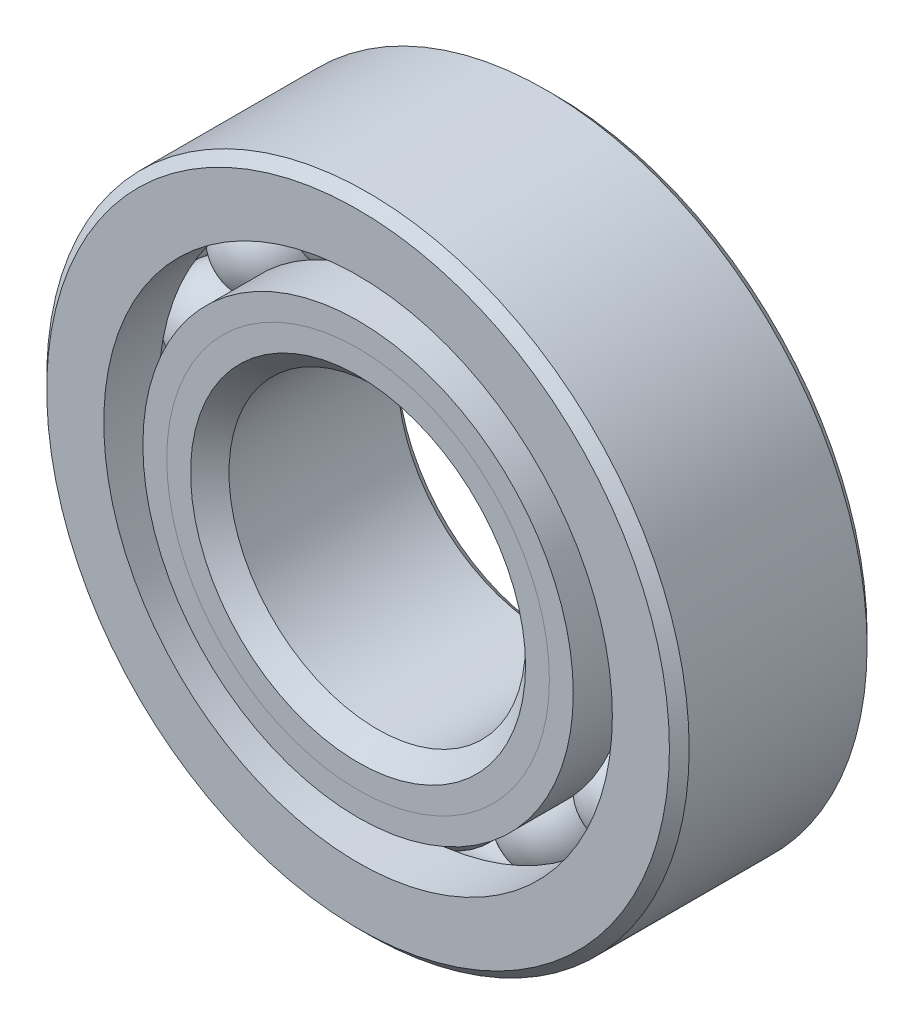
SolidWorks part; units mm, degrees
ref_plane "Front Plane" through (0, 0, 0) normal (0, 0, 1) x (1, 0, 0)
ref_plane "Top Plane" through (0, 0, 0) normal (0, 1, 0) x (1, 0, 0)
ref_plane "Right Plane" through (0, 0, 0) normal (1, 0, 0) x (0, 0, -1)
sketch "Sketch1" plane through (0, 0, 0) normal (1, 0, 0) x (0, 0, -1)
  line L0 (-6.35, 0) -> (6.35, 0) construction
  line L1 (0, 20.6375) -> (0, -20.6375) construction
  line L2 (5.715, 20.6375) -> (-5.715, 20.6375)
  line L3 (-5.715, 20.6375) -> (-6.35, 20.0025)
  line L4 (-6.35, 20.0025) -> (-6.35, 16.3373)
  line L5 (-6.35, 16.3373) -> (-2.8222, 16.3373)
  line L6 (6.35, 16.3373) -> (2.8222, 16.3373)
  line L7 (6.35, 20.0025) -> (6.35, 16.3373)
  line L8 (5.715, 20.6375) -> (6.35, 20.0025)
  line L9 (0, 20.6375) -> (0, 15.0813) construction
  line L10 (0, 15.0813) -> (0, 9.525) construction
  arc A0 (-2.8222, 16.3373) -> (2.8222, 16.3373) centre (0, 15.0813) cw
  point P14 (0, 9.525)
  dimension "D3" = 5.6444
  dimension "D1" = 45
  dimension "Width" = 12.7
  dimension "OD" = 41.275
  dimension "D2" = 0.635
  dimension "Shaft Dia" = 19.05
  dimension "D4" = 1.256
revolve "Revolve1" add sketch "Sketch1" angle 360 about L0
sketch "Sketch2" plane through (0, 0, 0) normal (1, 0, 0) x (0, 0, -1)
  line L0 (-6.35, 13.8252) -> (-2.8222, 13.8252)
  line L1 (-6.35, 20.0025) -> (-6.35, -20.0025) construction
  line L2 (-6.35, 13.8252) -> (-6.35, 12.2919)
  line L3 (-6.35, 12.2919) -> (-4.8167, 10.7586)
  line L4 (-4.8167, 10.7586) -> (0, 10.7586)
  line L5 (0, 20.6375) -> (0, -20.6375) construction
  line L6 (0, 10.7586) -> (0, 11.9921)
  line L7 (0, 11.9921) -> (0, 9.525) construction
  line L8 (-6.35, 13.8252) -> (-6.35, 10.7586) construction
  line L9 (-6.35, 10.7586) -> (-4.8167, 10.7586) construction
  arc A0 (-2.8222, 13.8252) -> (0, 11.9921) centre (0, 15.0813) ccw
  arc A1 (2.8222, 16.3373) -> (-2.8222, 16.3373) centre (0, 15.0813) ccw construction
  circle A2 centre (0, 15.0813) radius 3.0891 construction
  dimension "D1" = 45
revolve "Revolve2" add sketch "Sketch2" angle 360 about L0
sketch "Sketch3" plane through (0, 0, 0) normal (1, 0, 0) x (0, 0, -1)
  line L0 (-6.35, 12.2919) -> (-4.8167, 10.7586)
  line L1 (-4.8167, 10.7586) -> (0, 10.7586)
  line L2 (0, 10.7586) -> (0, 11.9921)
  line L3 (-6.35, 12.2919) -> (-6.35, 10.7586)
  line L4 (-6.35, 13.8252) -> (-6.35, 10.7586) construction
  line L5 (-6.35, 10.7586) -> (-5.1164, 9.525)
  line L6 (-5.1164, 9.525) -> (5.715, 9.525)
  line L7 (5.715, 20.6375) -> (5.715, -20.6375) construction
  line L8 (5.715, 9.525) -> (6.35, 10.16)
  line L9 (6.35, -20.0025) -> (6.35, 20.0025) construction
  line L10 (6.35, 10.16) -> (6.35, 13.8252)
  line L11 (6.35, 13.8252) -> (2.8222, 13.8252)
  line L13 (5.715, 20.6375) -> (6.35, 20.0025) construction
  circle A0 centre (0, 15.0813) radius 3.0891 construction
  arc A1 (2.8222, 13.8252) -> (0, 11.9921) centre (0, 15.0813) cw
revolve "Revolve3" add sketch "Sketch3" angle 360 about L0
sketch "Sketch4" plane through (0, 0, 0) normal (1, 0, 0) x (0, 0, -1)
  line L0 (-3.0891, 15.0813) -> (3.0891, 15.0813)
  circle A1 centre (0, 15.0813) radius 3.0891 construction
  arc A2 (-3.0891, 15.0813) -> (3.0891, 15.0813) centre (0, 15.0813) cw
  arc A3 (2.8222, 16.3373) -> (-2.8222, 16.3373) centre (0, 15.0813) ccw construction
revolve "Revolve4" add sketch "Sketch4" angle 360 about L0
ref_axis "Axis1" through (0, 0, -6.35) along (0, 0, 1)
pattern_circular "CirPattern1" count 14 every 25.714 about axis through (0, 0, -6.35) along (0, 0, 1) of bodies 104
equation "\"D2@Sketch1\" = \"Width@Sketch1\"*.05"
equation "\"D3@Sketch1\" = \"Width@Sketch1\"/2.25"
equation "\"D4@Sketch1\" = (((\"OD@Sketch1\"-\"Width@Sketch1\")/2)/3.25)/3.5"
equation "\"D2@CirPattern1\" = 360/\"Balls@CirPattern1\""
